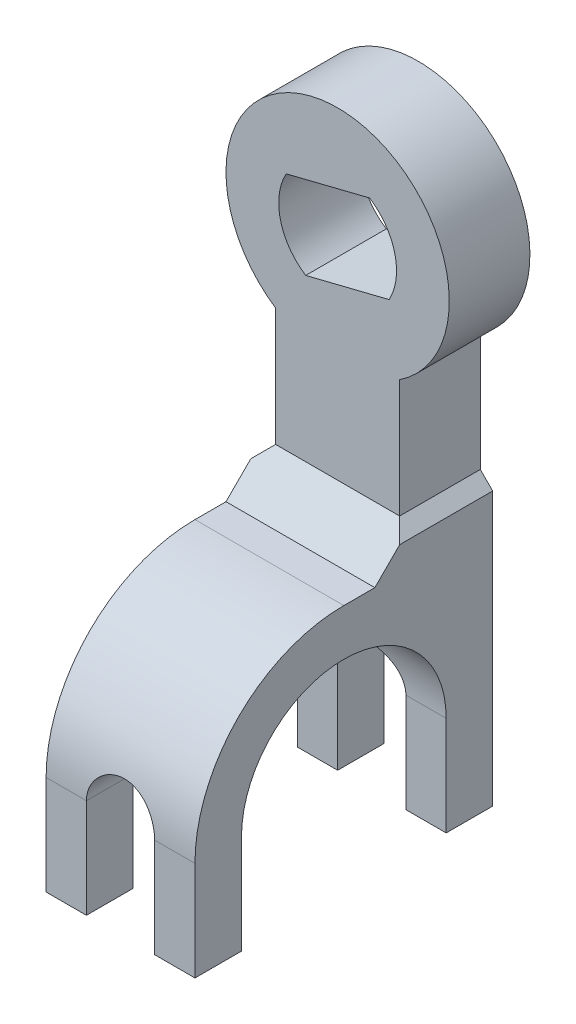
SolidWorks part; units mm, degrees
ref_plane "Front Plane" through (0, 0, 0) normal (0, 0, 1) x (1, 0, 0)
ref_plane "Top Plane" through (0, 0, 0) normal (0, 1, 0) x (1, 0, 0)
ref_plane "Right Plane" through (0, 0, 0) normal (1, 0, 0) x (0, 0, -1)
sketch "Sketch1" plane through (0, 0, 0) normal (0, 0, 1) x (1, 0, 0)
  line L0 (4.6089, 1.1491) -> (-4.6089, -1.1491) construction
  line L1 (2.575, 3.9915) -> (-4.1474, 2.3154)
  line L2 (4.1474, -2.3154) -> (-2.575, -3.9915)
  line L3 (-5, -7.4833) -> (-5, -22)
  line L4 (-5, -22) -> (5, -22)
  line L5 (0, -55) -> (0, 55) construction
  line L6 (5, -7.4833) -> (5, -22)
  line L7 (55, 0) -> (-55, 0) construction
  arc A0 (4.1474, -2.3154) -> (2.575, 3.9915) centre (0, 0) ccw
  arc A1 (5, -7.4833) -> (-5, -7.4833) centre (0, 0) ccw
  arc A2 (-4.1474, 2.3154) -> (-2.575, -3.9915) centre (0, 0) ccw
  point P16 (0, -22)
  dimension "D2" = 4.75
  dimension "D3" = 18
  dimension "D1" = 6.5
  dimension "D4" = 22
  dimension "D5" = 10
  dimension "D6" = 14
extrude "Boss-Extrude1" add sketch "Sketch1" along normal blind 6.5
sketch "Sketch2" plane through (0, 0, 0) normal (1, 0, 0) x (0, 0, -1)
  line L0 (-27.4459, -32) -> (12.5989, -32) construction
  line L1 (-12, -20) -> (0, -20)
  line L2 (0, -20) -> (0, -40)
  line L6 (8.8, 0) -> (-8.8, 0) construction
  line L7 (-12, -32) -> (-12, -5.7018) construction
  line L8 (0, 9.9) -> (0, -9.9) construction
  line L9 (-12, -32) -> (-12, -45.1164) construction
  line L10 (-3.75, -32) -> (-3.75, -40)
  line L11 (-20.25, -32) -> (-20.25, -40)
  line L12 (-20.25, -40) -> (-24, -40)
  line L13 (-24, -40) -> (-24, -32)
  line L14 (0, -40) -> (-3.75, -40)
  arc A2 (-3.75, -32) -> (-20.25, -32) centre (-12, -32) ccw
  arc A4 (-12, -20) -> (-24, -32) centre (-12, -32) ccw
  point P10 (-12, -38.5582)
  dimension "D1" = 32
  dimension "D2" = 12
  dimension "D3" = 16.5
  dimension "D4" = 8
extrude "Boss-Extrude2" add sketch "Sketch2" along normal mid plane 12
sketch "Sketch4" plane through (0, 0, 24) normal (0, 0, 1) x (1, 0, 0)
  line L0 (6, -32) -> (-6, -32) construction
  line L1 (-2.75, -32) -> (-2.75, -40)
  line L2 (6, -40) -> (-6, -40) construction
  line L3 (-2.75, -40) -> (2.75, -40)
  line L4 (0, -3.575) -> (0, 3.575) construction
  line L5 (2.75, -32) -> (2.75, -40)
  arc A0 (2.75, -32) -> (-2.75, -32) centre (0, -32) ccw
  point P12 (0, -40)
  dimension "D1" = 5.5
extrude "Cut-Extrude1" cut sketch "Sketch4" against normal through all
chamfer "Chamfer1" distance 3 angle 45 3 edges at (-5, -20, 3.25) (0, -20, 6.5) (5, -20, 3.25)
